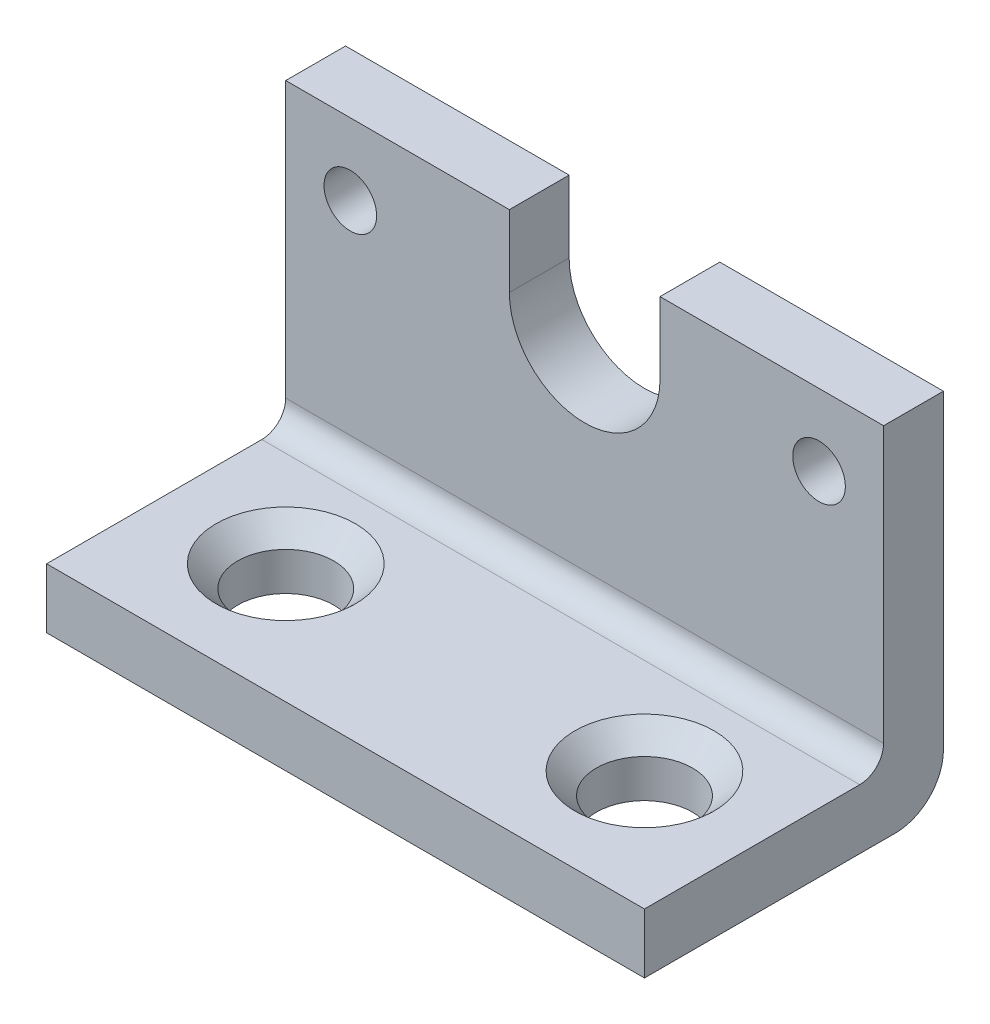
SolidWorks part; units mm, degrees
ref_plane "Front Plane" through (0, 0, 0) normal (0, 0, 1) x (1, 0, 0)
ref_plane "Top Plane" through (0, 0, 0) normal (0, 1, 0) x (1, 0, 0)
ref_plane "Right Plane" through (0, 0, 0) normal (1, 0, 0) x (0, 0, -1)
sketch "Sketch1" plane through (0, 0, 0) normal (0, 0, 1) x (1, 0, 0)
  line L0 (-4.0005, 15.24) -> (-4.0005, 19.05)
  line L1 (-15.875, 19.05) -> (-4.0005, 19.05)
  line L2 (-15.875, 19.05) -> (-15.875, 0)
  line L3 (-15.875, 0) -> (15.875, 0)
  line L4 (15.875, 19.05) -> (15.875, 0)
  line L5 (-15.875, 19.05) -> (15.875, 0) construction
  line L6 (-15.875, 0) -> (15.875, 19.05) construction
  line L7 (4.0005, 15.24) -> (4.0005, 19.05)
  line L8 (0, 15.24) -> (0, 23.3212) construction
  line L9 (4.0005, 19.05) -> (15.875, 19.05)
  arc A0 (-4.0005, 15.24) -> (4.0005, 15.24) centre (0, 15.24) ccw
  circle A1 centre (12.446, 15.24) radius 1.397
  circle A2 centre (-12.446, 15.24) radius 1.397
  point P0 (0, 9.525)
  dimension "D3" = 8.001
  dimension "D5" = 2.794
  dimension "D1" = 31.75
  dimension "D2" = 19.05
  dimension "D4" = 15.24
  dimension "D6" = 24.892
extrude "Boss-Extrude1" add sketch "Sketch1" against normal blind 3.175
sketch "Sketch2" plane through (0, 0, 0) normal (0, 1, 0) x (1, 0, 0)
  line L0 (0, -12.7) -> (0, 0) construction
  line L1 (-15.875, -12.7) -> (15.875, -12.7)
  line L2 (-15.875, -12.7) -> (-15.875, 0)
  line L3 (-15.875, 0) -> (15.875, 0)
  line L4 (15.875, -12.7) -> (15.875, 0)
  line L5 (-15.875, -12.7) -> (15.875, 0) construction
  line L6 (-15.875, 0) -> (15.875, -12.7) construction
  circle A0 centre (-9.525, -6.35) radius 2.5527
  circle A1 centre (9.525, -6.35) radius 2.5527
  point P0 (0, -6.35)
  dimension "D2" = 5.1054
  dimension "D1" = 12.7
  dimension "D3" = 19.05
extrude "Boss-Extrude2" add sketch "Sketch2" along normal blind 3.175
fillet "Fillet1" radius 1.27 1 edges
fillet "Fillet2" radius 2.54 1 edges at (0, 0, -3.175)
chamfer "Chamfer1" distance 1.143 angle 45 2 edges at (-9.525, 3.175, 8.9027) (9.525, 3.175, 8.9027)
